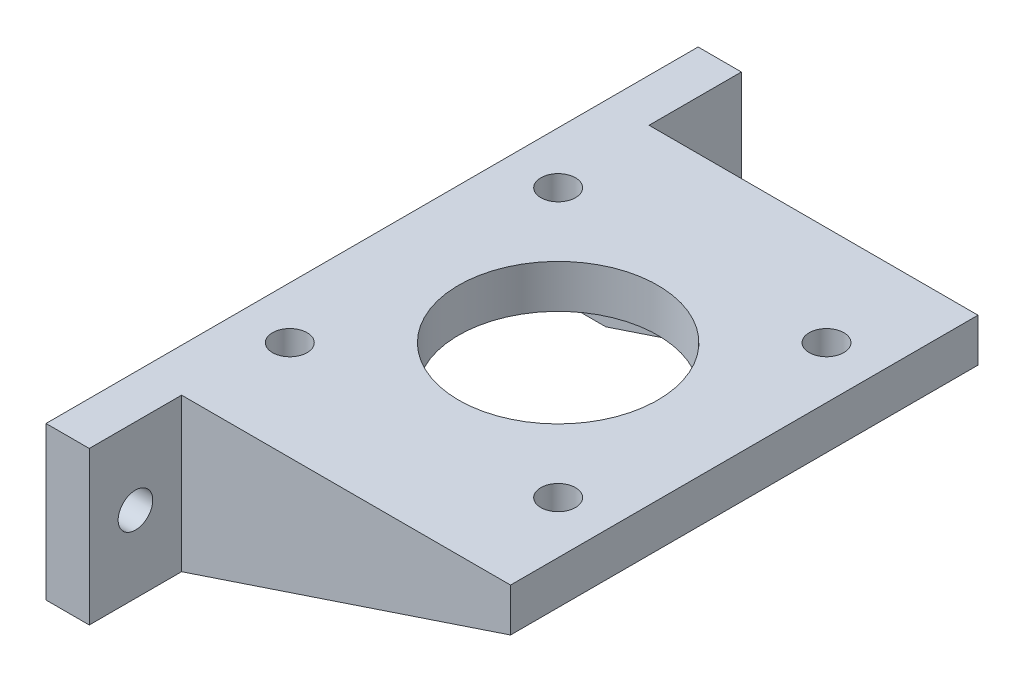
SolidWorks part; units mm, degrees
note: The reader was unsure of these and kept them because the rebuilt part matched: shared geometry of "Sketch1<3>", "Sketch1<4>".
material "ABS"
ref_plane "Front Plane" through (0, 0, 0) normal (0, 0, 1) x (1, 0, 0)
ref_plane "Top Plane" through (0, 0, 0) normal (0, 1, 0) x (1, 0, 0)
ref_plane "Right Plane" through (0, 0, 0) normal (1, 0, 0) x (0, 0, -1)
sketch "Sketch1" plane through (0, 0, 0) normal (0, 0, 1) x (1, 0, 0)
  line L0 (5, 5) -> (43, 5)
  line L1 (0, 0) -> (5, 0)
  line L2 (0, 0) -> (0, 5)
  line L3 (0, 5) -> (5, 5)
  line L4 (5, 0) -> (5, 5)
  line L5 (43, 5) -> (43, 0)
  line L6 (43, 0) -> (5, 0)
  line L7 (5, 0) -> (5, -12.666)
  line L8 (5, -12.666) -> (0, -12.666)
  line L9 (0, -12.666) -> (0, 0)
  line L10 (5, -12.666) -> (43, 0)
  dimension "D1" = 5
  dimension "D2" = 5
  dimension "D3" = 43
  dimension "D4" = 12.666
extrude "Boss-Extrude1" add sketch "Sketch1" against normal blind 44 contours L1 L4 L3 L2 | L6 L5 L0 L4
sketch "Sketch2" plane through (0, 5, 0) normal (0, 1, 0) x (1, 0, 0)
  line L3 (0, 44) -> (0, 0) construction
  line L4 (0, 0) -> (43, 0) construction
  circle A0 centre (21.5, 22) radius 11.5
  circle A1 centre (37, 37.5) radius 2
  circle A2 centre (6, 37.5) radius 2
  circle A3 centre (6, 6.5) radius 2
  circle A4 centre (37, 6.5) radius 2
  dimension "D3" = 23
  dimension "D4" = 4
  dimension "D1" = 21.5
  dimension "D2" = 22
  dimension "D5" = 15.5
  dimension "D6" = 15.5
  dimension "D7" = 2
  dimension "D8" = 2
extrude "Cut-Extrude1" cut sketch "Sketch2" against normal through all
extrude "Boss-Extrude2" add sketch "Sketch1<3>" along normal blind 5 contours L7 L10 L6 | L6 L5 L0 L4 | L1 L4 L3 L2 | L9 L8 L7 L1
sketch "Sketch1<3>" plane through (0, 0, 0) normal (0, 0, 1) x (1, 0, 0) same geometry as "Sketch1"
extrude "Boss-Extrude3" add sketch "Sketch1<4>" against normal blind 5 from vertex at -44 contours L1 L4 L3 L2 | L9 L8 L7 L1 | L7 L10 L6 | L6 L5 L0 L4
sketch "Sketch1<4>" plane through (0, 0, 0) normal (0, 0, 1) x (1, 0, 0) same geometry as "Sketch1"
sketch "Sketch3" plane through (0, 0, 0) normal (-1, 0, 0) x (0, 0, 1)
  line L0 (5, -12.666) -> (0, -12.666) construction
  line L1 (5, 5) -> (15.666, 5)
  line L2 (5, 5) -> (5, -12.666)
  line L3 (5, -12.666) -> (15.666, -12.666)
  line L4 (15.666, 5) -> (15.666, -12.666)
  line L5 (10.333, 5) -> (10.333, -12.666) construction
  line L6 (15.666, -3.833) -> (5, -3.833) construction
  line L7 (-22, 5) -> (-22, 0) construction
  line L8 (-49, 5) -> (5, 5) construction
  line L9 (-44, 0) -> (0, 0) construction
  line L10 (-49, -12.666) -> (-59.666, -12.666)
  line L11 (-59.666, 5) -> (-59.666, -12.666)
  line L12 (-54.333, 5) -> (-54.333, -12.666) construction
  line L13 (-59.666, -3.833) -> (-49, -3.833) construction
  line L14 (-49, 5) -> (-49, -12.666)
  line L15 (-49, 5) -> (-59.666, 5)
  circle A0 centre (10.333, -3.833) radius 2
  circle A1 centre (-54.333, -3.833) radius 2
  dimension "D2" = 4
  dimension "D1" = 10.666
extrude "Boss-Extrude4" add sketch "Sketch3" against normal blind 5
equation "\"rod_diameter\"= 8"
equation "\"rod_hole_thickness\"= 4"
equation "\"rod_radius\"= \"rod_diameter\" / 2"
equation "\"platter_diameter\"= 320"
equation "\"platter_radius\"= \"platter_diameter\" / 2"
equation "\"extruder_mount_hole_spacing\"= 75"
equation "\"arm_rod_spacing\"= 40"
equation "\"D2@Sketch2\" = \"D1@Boss-Extrude1\" / 2"
equation "\"motor_level_rod_spacing\"= 15"
equation "\"top_frame_spacing\"= 90"
equation "\"linear_bearing_diameter\"= 15"
equation "\"z_rod_spacing\"= 75"
equation "\"platter_rod_spacing\"= 50"
equation "\"rod_nut_thickness\"= 6.5"
equation "\"rod_nut_inscribed_diameter\"= 13"
equation "\"z_height\"= 400"
equation "\"gear_pitch\"=2"
equation "\"r_gear_teeth\"= 450"
equation "\"theta_gear_teeth\"= 385"
equation "\"sheet_thickness\"=5.333"
equation "\"sheet_tab_hole_thickness\"= \"sheet_thickness\""
equation "\"sheet_tab_width\"= \"sheet_thickness\"*2"
equation "\"sheet_bolt_diameter\"= 3"
equation "\"sheet_bolt_length\"= 16"
equation "\"sheet_nut_diameter\"= 5.5"
equation "\"sheet_nut_thickness\"= 2.5"
equation "\"sheet_nut_depth\"= 10"
equation "\"bearing_outside_diameter\"= 22"
equation "\"bearing_thickness\"= 7"
equation "\"corner_part_thickness\"= \"sheet_thickness\" + \"bearing_thickness\""
equation "\"D4@Sketch1\"=\"sheet_thickness\"*2+7-\"D1@Sketch1\""
equation "\"D1@Sketch2\"= \"D3@Sketch1\" / 2"
equation "\"D1@Sketch3\"=\"sheet_thickness\"*2"
equation "\"D2@Sketch3\"=\"sheet_bolt_diameter\"+\"printed_hole_tolerance\""
equation "\"z_drive_rod_offset\"= 12"
equation "\"sheet_double_tab_width\"= 35"
equation "\"setscrew_nut_diameter\"= 6"
equation "\"setscrew_nut_thickness\"= 3"
equation "\"setscrew_bolt_diameter\"= 3"
equation "\"motor_shaft_diameter\"= 5.7"
equation "\"printed_hole_tolerance\"= 1"
equation "\"D4@Sketch2\"=3 +\"printed_hole_tolerance\""
equation "\"D3@Sketch2\"=22 +\"printed_hole_tolerance\""
